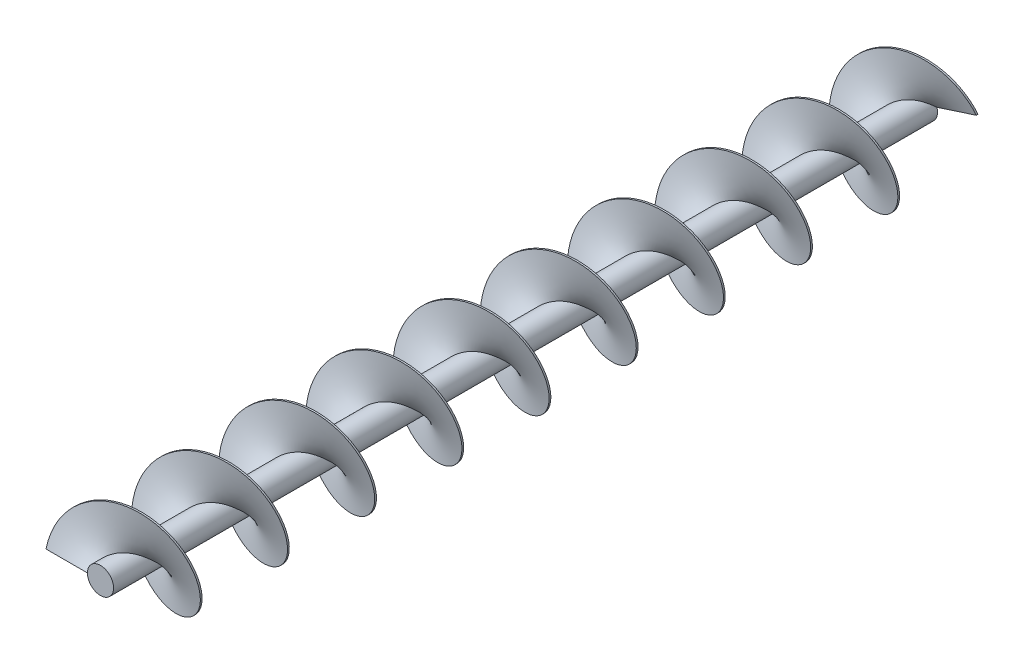
SolidWorks part; units mm, degrees
ref_plane "Front Plane" through (0, 0, 0) normal (0, 0, 1) x (1, 0, 0)
ref_plane "Top Plane" through (0, 0, 0) normal (0, 1, 0) x (1, 0, 0)
ref_plane "Right Plane" through (0, 0, 0) normal (1, 0, 0) x (0, 0, -1)
sketch "Sketch1" plane through (0, 0, 0) normal (0, 0, 1) x (1, 0, 0)
  circle A0 centre (0, 0) radius 1.905
  dimension "D1" = 3.81
extrude "Boss-Extrude1" add sketch "Sketch1" along normal mid plane 120.015
sketch "Sketch4" plane through (0, 0, 60.0075) normal (0, 0, 1) x (1, 0, 0)
  circle A0 centre (0, 0) radius 7.9375
  dimension "D1" = 15.875
curve "Helix/Spiral1" pitch 12.7 height 120.015 radius 7.9375 centre (0, 0, 60.0075) axis (0, 0, -1) start towards (-1, 0, 0)
sketch "Sketch5" plane through (0, 0, 0) normal (0, 1, 0) x (1, 0, 0)
  line L5 (-1.905, -60.0075) -> (-7.9375, -60.0075)
  line L6 (-7.9375, -60.0075) -> (-7.9375, -59.7535)
  line L7 (-7.9375, -59.7535) -> (-1.905, -59.7535)
  line L8 (-1.905, 60.0075) -> (-1.905, -60.0075) construction
  line L9 (-1.905, -59.7535) -> (-1.905, -60.0075)
  line L10 (0, -60.0075) -> (-7.9375, -60.0075) construction
  line L11 (-1.905, -60.0075) -> (1.905, -60.0075) construction
  dimension "D1" = 7.9375
  dimension "D2" = 0.254
sweep "Sweep1" add profiles "Sketch5" path "Helix/Spiral1"
sketch "Sketch6" plane through (0, 0, -60.0075) normal (0, 0, -1) x (-1, 0, 0)
  line L4 (-0.381, 0) -> (0.381, 0)
  line L5 (0.381, 0) -> (0.381, 1.524)
  line L6 (0.381, 1.524) -> (-0.381, 1.524)
  line L7 (-0.381, 1.524) -> (-0.381, 0)
  circle A0 centre (0, 0) radius 1.27
  point P6 (0, 0)
  dimension "D1" = 2.54
  dimension "D2" = 1.524
  dimension "D3" = 0.762
extrude "Cut-Extrude1" cut sketch "Sketch6" against normal blind 12.7 contours L7 L4 L5 L6 | A0
equation "\"Spiral\"= .625 / 2"
equation "\"D1@Sketch4\"=\"Spiral\"*2"
equation "\"D1@Sketch5\"=\"Spiral\""
equation "\"Aug L\"= 4.725"
equation "\"Aug W\"= .15"
equation "\"D1@Boss-Extrude1\"=\"Aug L\""
equation "\"D1@Sketch1\"=\"Aug W\""
